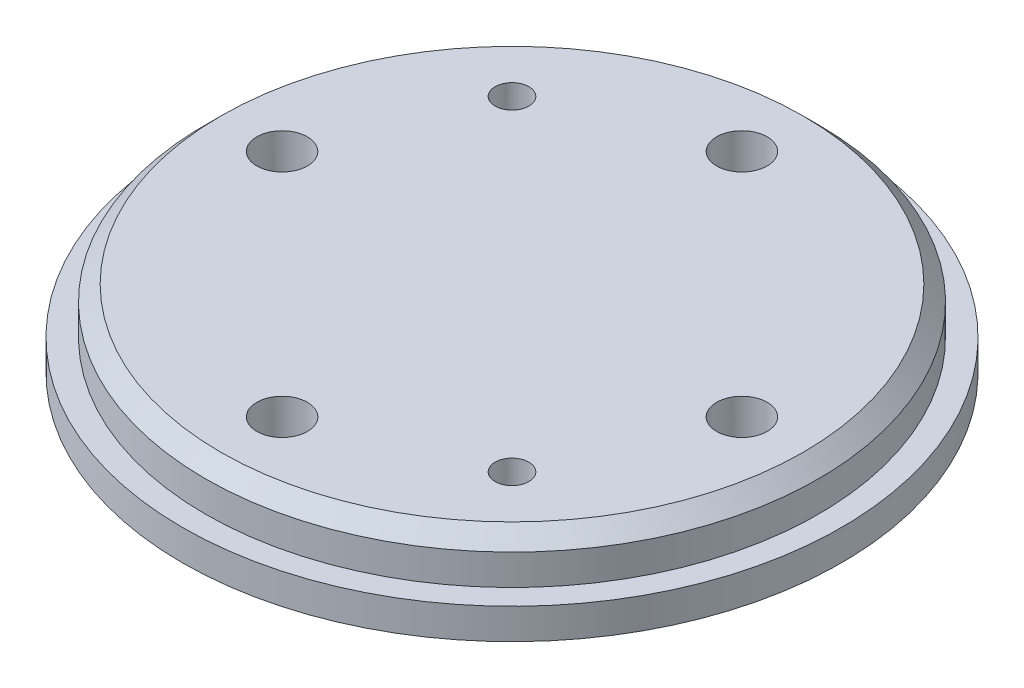
SolidWorks part; units mm, degrees
ref_plane "前视基准面" through (0, 0, 0) normal (0, 0, 1) x (1, 0, 0)
ref_plane "上视基准面" through (0, 0, 0) normal (0, 1, 0) x (1, 0, 0)
ref_plane "右视基准面" through (0, 0, 0) normal (1, 0, 0) x (0, 0, -1)
sketch "草图1" plane through (0, 0, 0) normal (0, 1, 0) x (1, 0, 0)
  circle A0 centre (0, 0) radius 21.5
  dimension "D1" = 43
extrude "凸台-拉伸1" add sketch "草图1" along normal blind 2
sketch "草图3" plane through (0, 2, 0) normal (0, 1, 0) x (1, 0, 0)
  circle A0 centre (0, 0) radius 20
  dimension "D1" = 40
extrude "凸台-拉伸2" add sketch "草图3" along normal blind 3
chamfer "倒角1" distance 1 angle 45 1 edges at (0, 5, 20)
sketch "草图4" plane through (0, 5, 0) normal (0, 1, 0) x (1, 0, 0)
  line L0 (0, 15) -> (0, 0) construction
  circle A0 centre (0, 15) radius 1.65
  dimension "D1" = 3.3
  dimension "D2" = 15
extrude "切除-拉伸1" cut sketch "草图4" against normal through all
chamfer "倒角2" distance 0.5 angle 45 1 edges at (0, 0, -13.35)
pattern_circular "阵列(圆周)1" count 4 over 360 about axis through (0, 2, 0) along (0, -1, 0) of "切除-拉伸1", "倒角2" reverse direction yes
sketch "草图5" plane through (0, 5, 0) normal (0, 1, 0) x (1, 0, 0)
  line L0 (-10.6066, 10.6066) -> (0, 0) construction
  circle A0 centre (-10.6066, 10.6066) radius 1.1
  dimension "D3" = 2.2
  dimension "D1" = 45
  dimension "D2" = 15
extrude "切除-拉伸2" cut sketch "草图5" against normal through all
sketch "草图6" plane through (0, 0, 0) normal (0, -1, 0) x (1, 0, 0)
  circle A0 centre (-10.6066, -10.6066) radius 2.1
  dimension "D1" = 4.2
extrude "切除-拉伸3" cut sketch "草图6" against normal blind 2
chamfer "倒角3" distance 1 angle 45 1 edges at (-10.6066, 2, -11.7066)
pattern_circular "阵列(圆周)2" count 2 over 360 about axis through (0, 2, 0) along (0, -1, 0) of "切除-拉伸2", "切除-拉伸3", "倒角3"
